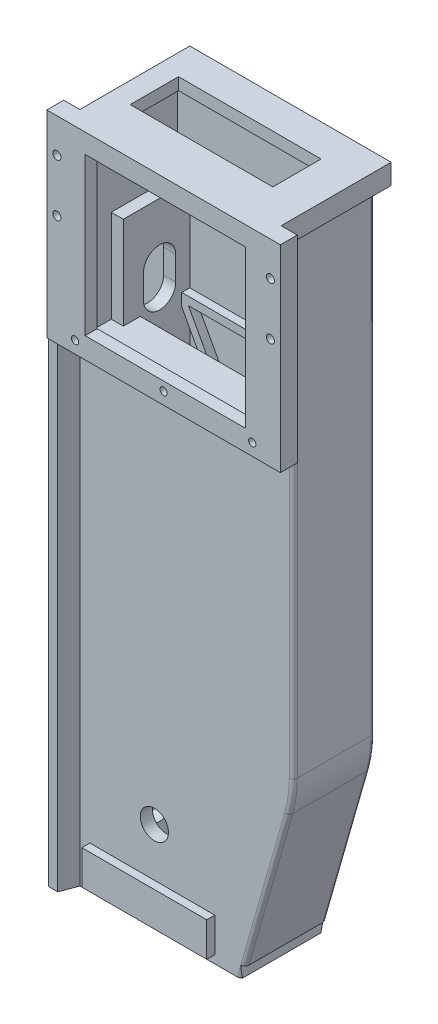
SolidWorks part; units mm, degrees
ref_plane "前视基准面" through (0, 0, 0) normal (0, 0, 1) x (1, 0, 0)
ref_plane "上视基准面" through (0, 0, 0) normal (0, 1, 0) x (1, 0, 0)
ref_plane "右视基准面" through (0, 0, 0) normal (1, 0, 0) x (0, 0, -1)
sketch "草图2" plane through (0, 0, 0) normal (0, 1, 0) x (1, 0, 0)
  line L0 (-163.1117, 0) -> (416.8883, 0)
  line L1 (-55, 0) -> (55, 0) construction
  line L2 (416.8883, 0) -> (416.8883, 42)
  line L3 (416.8883, 42) -> (376.8883, 42)
  line L4 (376.8883, 42) -> (376.8883, 315)
  line L5 (376.8883, 315) -> (-123.1117, 315)
  line L6 (-123.1117, 315) -> (-123.1117, 42)
  line L7 (-123.1117, 42) -> (-163.1117, 42)
  line L8 (-163.1117, 42) -> (-163.1117, 0)
  dimension "D2" = 40
  dimension "D3" = 40
  dimension "D4" = 315
  dimension "D5" = 42
  dimension "D6" = 42
  dimension "D11" = 500
sketch "草图3" plane through (0, 0, 0) normal (0, 1, 0) x (1, 0, 0)
  line L0 (-123.1117, 315) -> (-123.1117, 42) construction
  line L1 (-71.1117, 235) -> (282.8883, 235)
  line L2 (-71.1117, 235) -> (-71.1117, 115)
  line L3 (-71.1117, 115) -> (282.8883, 115)
  line L4 (282.8883, 235) -> (282.8883, 115)
  line L5 (-163.1117, 0) -> (416.8883, 0) construction
  dimension "D1" = 52
  dimension "D2" = 115
  dimension "D3" = 354
  dimension "D4" = 120
extrude "凸台-拉伸1" add sketch "草图2" against normal blind 50
sketch "草图5" plane through (0, -50, 0) normal (0, -1, 0) x (1, 0, 0)
  line L0 (-123.1117, -285) -> (366.8883, -285)
  line L1 (-123.1117, -315) -> (-123.1117, -42) construction
  line L2 (376.8883, -315) -> (-123.1117, -315) construction
  line L3 (376.8883, -42) -> (376.8883, -315) construction
  line L4 (366.8883, -285) -> (366.8883, -42)
  line L5 (366.8883, -42) -> (416.8883, -42)
  line L6 (416.8883, -42) -> (416.8883, 0)
  line L7 (55, 0) -> (-55, 0) construction
  line L8 (416.8883, 0) -> (-163.1117, 0)
  line L9 (-163.1117, -42) -> (-163.1117, 0) construction
  line L10 (-163.1117, 0) -> (-163.1117, -42)
  line L11 (-163.1117, -42) -> (-123.1117, -42)
  line L12 (-123.1117, -42) -> (-123.1117, -285)
  dimension "D1" = 30
  dimension "D2" = 10
extrude "凸台-拉伸2" add sketch "草图5" along normal blind 440
sketch "草图6" plane through (0, -490, 0) normal (0, -1, 0) x (1, 0, 0)
  line L0 (366.8883, -285) -> (366.8883, -82)
  line L1 (366.8883, -285) -> (366.8883, -42) construction
  line L2 (366.8883, -82) -> (-123.1117, -82)
  line L3 (-123.1117, -42) -> (-123.1117, -285) construction
  line L4 (-123.1117, -82) -> (-123.1117, -285)
  line L5 (-123.1117, -285) -> (366.8883, -285)
  line L6 (366.8883, -42) -> (416.8883, -42) construction
  dimension "D1" = 40
extrude "凸台-拉伸3" add sketch "草图6" along normal blind 1220
sketch "草图7" plane through (0, 0, -285) normal (0, 0, -1) x (-1, 0, 0)
  line L0 (-236.8883, -1680) -> (-246.8883, -1680)
  line L1 (123.1117, -1710) -> (-366.8883, -1710) construction
  line L2 (-236.8883, -1710) -> (-236.8883, -1680)
  line L4 (-366.8883, -1710) -> (-366.8883, -50) construction
  line L5 (-366.8883, -1260) -> (-366.8883, -1710)
  line L6 (-366.8883, -1710) -> (-236.8883, -1710)
  line L7 (-246.8883, -1680) -> (-366.8883, -1260)
  dimension "D1" = 360
  dimension "D2" = 30
  dimension "D3" = 450
  dimension "D4" = 10
extrude "切除-拉伸3" cut sketch "草图7" against normal up to next
fillet "圆角1" radius 300 1 edges at (366.8883, -1260, -183.5)
fillet "圆角5" radius 10 3 edges at (366.8883, -633.9918, -285) (363.9886, -1259.5939, -285) (301.1169, -1490.1999, -285)
fillet "圆角6" radius 10 3 edges at (301.1169, -1490.1999, -82) (363.9886, -1259.5939, -82) (366.8883, -853.9918, -82)
sketch "草图8" plane through (-123.1117, 0, 0) normal (-1, 0, 0) x (0, 0, 1)
  line L0 (-82, -1710) -> (-285, -1710) construction
  line L1 (-120, -1710) -> (-240, -1710)
  line L2 (-120, -1710) -> (-120, -260)
  line L3 (-120, -260) -> (-240, -260)
  line L4 (-240, -1710) -> (-240, -260)
  line L5 (55, 0) -> (-55, 0) construction
  line L6 (-285, -1710) -> (-285, -50) construction
  dimension "D1" = 260
  dimension "D2" = 45
  dimension "D3" = 120
extrude "切除-拉伸4" cut sketch "草图8" against normal blind 30
shell "抽壳3" thickness 30 removed face at (25.2308, -1710, -182.1)
ref_plane "基准面1" through (0, -260, 0) normal (0, 1, 0) x (1, 0, 0)
sketch "草图9" plane through (0, -260, 0) normal (0, 1, 0) x (1, 0, 0)
  line L0 (-123.1117, 285) -> (-153.1117, 285)
  line L1 (-153.1117, 285) -> (-168.1117, 319.5)
  line L2 (-168.1117, 319.5) -> (-198.1117, 319.5)
  line L3 (-198.1117, 319.5) -> (-198.1117, 349.5)
  line L4 (-198.1117, 349.5) -> (-228.1117, 349.5)
  line L5 (-228.1117, 349.5) -> (-228.1117, 227.5)
  line L6 (-228.1117, 227.5) -> (-191.1117, 227.5)
  line L7 (-191.1117, 227.5) -> (-191.1117, 240)
  line L8 (-191.1117, 240) -> (-123.1117, 240)
  line L9 (-123.1117, 240) -> (-123.1117, 285)
  dimension "D1" = 30
  dimension "D2" = 30
  dimension "D3" = 30
  dimension "D4" = 105
  dimension "D5" = 30
  dimension "D6" = 37
  dimension "D7" = 12.5
  dimension "D8" = 122
extrude "凸台-拉伸4" add sketch "草图9" against normal up to surface (1450 mm away) up to face at (71.8883, -1710, -183.5)
sketch "草图10" plane through (0, -260, 0) normal (0, -1, 0) x (1, 0, 0)
  line L0 (-116.1117, -240) -> (-116.1117, -285)
  line L1 (-93.1117, -240) -> (-191.1117, -240) construction
  line L2 (-191.1117, -240) -> (-123.1117, -240) construction
  line L3 (-123.1117, -285) -> (-153.1117, -285) construction
  line L4 (-153.1117, -285) -> (227.9167, -285) construction
  line L5 (-116.1117, -285) -> (-153.1117, -285)
  line L6 (-153.1117, -285) -> (-168.1117, -319.5)
  line L7 (-168.1117, -319.5) -> (-198.1117, -319.5)
  line L8 (-198.1117, -319.5) -> (-198.1117, -349.5)
  line L9 (-198.1117, -349.5) -> (-228.1117, -349.5)
  line L10 (-228.1117, -349.5) -> (-228.1117, -227.5)
  line L11 (-228.1117, -227.5) -> (-191.1117, -227.5)
  line L12 (-191.1117, -227.5) -> (-191.1117, -240)
  line L13 (-191.1117, -240) -> (-116.1117, -240)
sketch "草图12" plane through (0, -1710, 0) normal (0, -1, 0) x (1, 0, 0)
  line L0 (-123.1117, -82) -> (-163.1117, -82)
  line L7 (-228.1117, -74.5) -> (-228.1117, -139.5)
  line L8 (-228.1117, -139.5) -> (-191.1117, -139.5)
  line L9 (-191.1117, -139.5) -> (-191.1117, -127)
  line L10 (-191.1117, -127) -> (-176.1117, -127)
  line L11 (-176.1117, -127) -> (-176.1117, -120)
  line L12 (-176.1117, -120) -> (-123.1117, -120)
  line L13 (-123.1117, -120) -> (-123.1117, -82)
  line L14 (-163.1117, -82) -> (-178.1117, -42)
  line L15 (-178.1117, -42) -> (-203.1117, -42)
  line L16 (-203.1117, -42) -> (-203.1117, -82)
  line L17 (-228.1117, -74.5) -> (-201.014, -88.7528)
  line L18 (-201.014, -88.7528) -> (-198.6865, -84.3276)
  line L19 (-198.6865, -84.3276) -> (-203.1117, -82)
  point P3 (-190.6117, -42)
  dimension "D1" = 40
  dimension "D2" = 15
  dimension "D3" = 105
  dimension "D4" = 37
  dimension "D5" = 12.5
  dimension "D6" = 65
  dimension "D7" = 7
  dimension "D8" = 15
  dimension "D9" = 40
  dimension "D10" = 25
  dimension "D11" = 40
  dimension "D12" = 5
  dimension "D13" = 5
extrude "凸台-拉伸7" add sketch "草图12" against normal up to surface (1450 mm away) up to plane "基准面1"
sketch "草图13" plane through (0, 0, -285) normal (0, 0, -1) x (-1, 0, 0)
  line L0 (-376.8883, -50) -> (123.1117, -50) construction
  line L4 (123.1117, -260) -> (123.1117, -50) construction
  line L5 (153.1117, -1710) -> (-227.9167, -1710) construction
  line L6 (153.1117, -1710) -> (153.1117, -260) construction
  circle A0 centre (-21.8883, -1485) radius 35
  circle A1 centre (-21.8883, -265) radius 35
  dimension "D1" = 70
  dimension "D2" = 70
  dimension "D5" = 225
  dimension "D6" = 175
  dimension "D3" = 215
  dimension "D4" = 145
extrude "切除-拉伸5" cut sketch "草图13" against normal through all
extrude "切除-拉伸1" cut sketch "草图3" against normal blind 50
sketch "草图15" plane through (0, 0, 0) normal (0, 0, 1) x (1, 0, 0)
  line L0 (-163.1117, 0) -> (416.8883, 0) construction
  line L1 (329.8883, -438) -> (-68.1117, -438)
  line L2 (329.8883, -438) -> (329.8883, -48)
  line L3 (329.8883, -48) -> (-68.1117, -48)
  line L4 (-68.1117, -438) -> (-68.1117, -48)
  line L5 (-163.1117, -490) -> (-163.1117, 0) construction
  dimension "D1" = 398
  dimension "D2" = 390
  dimension "D3" = 48
  dimension "D4" = 95
extrude "切除-拉伸6" cut sketch "草图15" against normal up to surface (30 mm away)
sketch "草图17" plane through (-93.1117, 0, 0) normal (-1, 0, 0) x (0, 0, 1)
  line L0 (-140, -370) -> (-140, -430)
  line L1 (-220, -430) -> (-220, -370)
  line L2 (-140, -600) -> (-140, -720)
  line L3 (-220, -720) -> (-220, -600)
  line L4 (-180, -525.5736) -> (-180, -50525.5736) construction
  line L5 (-140, -1120) -> (-140, -1000)
  line L6 (-220, -1000) -> (-220, -1120)
  line L7 (-140, -1530) -> (-140, -1430)
  line L8 (-220, -1530) -> (-220, -1430)
  line L9 (173.25, -260) -> (-173.25, -260) construction
  arc A0 (-140, -370) -> (-220, -370) centre (-180, -370) ccw
  arc A1 (-220, -430) -> (-140, -430) centre (-180, -430) ccw
  arc A2 (-140, -600) -> (-220, -600) centre (-180, -600) ccw
  arc A3 (-220, -720) -> (-140, -720) centre (-180, -720) ccw
  arc A4 (-140, -1000) -> (-220, -1000) centre (-180, -1000) ccw
  arc A5 (-220, -1120) -> (-140, -1120) centre (-180, -1120) ccw
  arc A6 (-140, -1430) -> (-220, -1430) centre (-180, -1430) ccw
  arc A7 (-220, -1530) -> (-140, -1530) centre (-180, -1530) ccw
  point P1 (-180, -330)
  point P9 (-180, -560)
  point P11 (-180, -470)
  point P13 (-180, -760)
  point P15 (-180, -960)
  point P17 (-180, -1160)
  point P34 (-180, -1390)
  dimension "D1" = 80
  dimension "D2" = 70
  dimension "D3" = 60
  dimension "D4" = 90
  dimension "D5" = 120
  dimension "D6" = 120
  dimension "D7" = 200
  dimension "D8" = 100
  dimension "D9" = 230
extrude "切除-拉伸7" cut sketch "草图17" against normal up to next
sketch "草图18" plane through (0, -1710, 0) normal (0, -1, 0) x (1, 0, 0)
  line L0 (236.8883, -86.9418) -> (236.8883, -280.0582) construction
  line L1 (206.8883, -255) -> (-63.1117, -255)
  line L2 (206.8883, -255) -> (206.8883, -112)
  line L3 (206.8883, -112) -> (-63.1117, -112)
  line L4 (-63.1117, -255) -> (-63.1117, -112)
  line L5 (181.8883, -245) -> (1.8883, -245)
  line L6 (181.8883, -245) -> (181.8883, -122)
  line L7 (181.8883, -122) -> (1.8883, -122)
  line L8 (1.8883, -245) -> (1.8883, -122)
  line L9 (-153.1117, -285) -> (227.9167, -285) construction
  line L11 (227.9167, -82) -> (-163.1117, -82) construction
  line L12 (-93.1117, -120) -> (-93.1117, -240) construction
  point P18 (-93.1117, -180)
  point P23 (-291.4725, -200.257)
  point P24 (-46.1117, -222)
  dimension "D1" = 55
  dimension "D2" = 40
  dimension "D3" = 40
  dimension "D4" = 95
extrude "凸台-拉伸8" add sketch "草图18" against normal blind 30
hole_wizard "M16 螺纹孔1" positions "草图21" profile "草图22" tap size "M16" standard "ISO" end condition through all
sketch "草图21" plane through (0, -1710, 0) normal (0, -1, 0) x (-1, 0, 0)
  point P0 (46.1447, 221.9951)
sketch "草图22" plane through (-46.1447, -1710, -221.9951) normal (1, 0, 0) x (0, 0, -1)
  line L0 (0, 0) -> (0, 1710)
  line L1 (0, 1710) -> (7, 1710)
  line L2 (7, 1710) -> (7, 0)
  line L5 (7, 0) -> (0, 0)
  line L11 (0, -6.35) -> (0, 107.95) construction
  dimension "螺纹线主直径" = 14
  dimension "通孔螺纹孔钻头深度" = 1710
chamfer "倒角1" distance 2 angle 45 5 edges at (-228.1117, -985, -227.5) (-228.1117, -985, -139.5) (-203.1117, -985, -42) (-228.1117, -985, -74.5) (-228.1117, -985, -349.5) first distance on face at (-209.6117, -985, -227.5) first distance on face at (-209.6117, -985, -139.5) first distance on face at (-203.1117, -985, -62) first distance on face at (-228.1117, -985, -107) first distance on face at (-213.1117, -985, -349.5)
ref_plane "基准面2" through (0, 0, -235) normal (0, 0, 1) x (1, 0, 0)
sketch "草图25" plane through (0, 0, -235) normal (0, 0, 1) x (1, 0, 0)
  line L0 (336.8883, -470) -> (-63.1117, -470)
  line L1 (336.8883, -30) -> (336.8883, -1217.9835) construction
  line L2 (-63.1117, -230) -> (-63.1117, -1680) construction
  line L3 (336.8883, -1210) -> (-56.1117, -1210)
  line L4 (282.8883, 0) -> (-71.1117, 0) construction
  line L5 (1.8883, -1710) -> (181.8883, -1710) construction
  dimension "D1" = 470
  dimension "D2" = 500
rib "筋10" sketch "草图25" sketch "草图25" thickness 20 extrusion direction normal to sketch draft on no parameters "D1"=20
sketch "草图26" plane through (0, 0, -235) normal (0, 0, 1) x (1, 0, 0)
  line L0 (336.8883, -1208.9918) -> (-63.1117, -470)
  line L1 (336.8883, -1217.9835) -> (336.8883, -1200) construction
  line L2 (-63.1117, -480) -> (-63.1117, -460) construction
  line L3 (336.8883, -470) -> (-63.1117, -1210)
  line L4 (336.8883, -480) -> (336.8883, -460) construction
  line L5 (-63.1117, -1220) -> (-63.1117, -1200) construction
rib "筋11" sketch "草图26" sketch "草图26" thickness 20 extrusion direction normal to sketch draft on no parameters "D1"=20
ref_plane "基准面3" through (0, 0, -132) normal (0, 0, -1) x (-1, 0, 0)
sketch "草图27" plane through (0, 0, -132) normal (0, 0, -1) x (-1, 0, 0)
  line L0 (63.1117, -470) -> (-336.8883, -470)
  line L1 (-336.8883, -1217.9835) -> (-336.8883, -460) construction
  line L3 (-336.8883, -1210) -> (63.1117, -1210)
  line L4 (63.1117, -460) -> (63.1117, -1680) construction
  line L7 (71.1117, 0) -> (-282.8883, 0) construction
  line L8 (-181.8883, -1710) -> (-1.8883, -1710) construction
  dimension "D1" = 470
  dimension "D2" = 500
rib "筋12" sketch "草图27" sketch "草图27" thickness 20 extrusion direction normal to sketch draft on no parameters "D1"=20
sketch "草图29" plane through (0, 0, -132) normal (0, 0, -1) x (-1, 0, 0)
  line L0 (63.1117, -1210) -> (-336.8883, -470)
  line L1 (63.1117, -1200) -> (63.1117, -1220) construction
  line L2 (-336.8883, -460) -> (-336.8883, -480) construction
  line L3 (63.1117, -470) -> (-336.8883, -1208.9918)
  line L4 (63.1117, -460) -> (63.1117, -480) construction
  line L5 (-336.8883, -1200) -> (-336.8883, -1217.9835) construction
rib "筋13" sketch "草图29" sketch "草图29" thickness 20 extrusion direction normal to sketch draft on no parameters "D1"=20
sketch "草图30" plane through (0, 0, -82) normal (0, 0, 1) x (1, 0, 0)
  line L0 (-163.1117, -260) -> (-163.1117, -1710) construction
  line L1 (171.8883, -1690) -> (-138.1117, -1690)
  line L2 (171.8883, -1690) -> (171.8883, -1605)
  line L3 (171.8883, -1605) -> (-138.1117, -1605)
  line L4 (-138.1117, -1690) -> (-138.1117, -1605)
  line L5 (227.9167, -1710) -> (-163.1117, -1710) construction
  dimension "D1" = 310
  dimension "D2" = 85
  dimension "D3" = 25
  dimension "D4" = 20
extrude "凸台-拉伸9" add sketch "草图30" along normal blind 20
sketch "草图31" plane through (0, 0, 0) normal (0, 0, 1) x (1, 0, 0)
  line L0 (416.8883, -490) -> (-163.1117, -490) construction
  line L1 (356.8883, -490) -> (-123.1117, -490) construction
  line L2 (-163.1117, -490) -> (-163.1117, 0) construction
  line L3 (-163.1117, 0) -> (416.8883, 0) construction
  line L4 (416.8883, -490) -> (416.8883, 0) construction
  circle A0 centre (346.8883, -460) radius 9
  circle A1 centre (126.8883, -460) radius 9
  circle A2 centre (-93.1117, -460) radius 9
  circle A3 centre (-138.1117, -215) radius 10
  circle A4 centre (-138.1117, -85) radius 10
  circle A5 centre (391.8883, -215) radius 10
  circle A6 centre (391.8883, -85) radius 10
  dimension "D1" = 18
  dimension "D2" = 18
  dimension "D3" = 18
  dimension "D4" = 30
  dimension "D10" = 20
  dimension "D11" = 20
  dimension "D12" = 20
  dimension "D13" = 20
  dimension "D20" = 25
  dimension "D21" = 25
  dimension "D5" = 30
  dimension "D6" = 30
  dimension "D7" = 70
  dimension "D8" = 220
  dimension "D9" = 220
  dimension "D14" = 25
  dimension "D15" = 25
  dimension "D16" = 85
  dimension "D17" = 215
  dimension "D18" = 85
  dimension "D19" = 215
extrude "切除-拉伸8" cut sketch "草图31" against normal up to surface (42 mm away) up to face at (-143.1117, -245, -42)
sketch "草图32" plane through (0, -1710, 0) normal (0, -1, 0) x (1, 0, 0)
  line L1 (236.8883, -86.9418) -> (236.8883, -280.0582) construction
  line L2 (227.9167, -82) -> (-163.1117, -82) construction
  line L3 (-228.1117, -76.5) -> (-228.1117, -137.5) construction
  line L4 (-178.1117, -42) -> (-201.1117, -42) construction
  circle A0 centre (-188.1117, -112) radius 7
  circle A1 centre (141.8883, -107) radius 7
  dimension "D1" = 95
  dimension "D3" = 14
  dimension "D4" = 14
  dimension "D2" = 25
  dimension "D5" = 40
  dimension "D6" = 70
extrude "切除-拉伸9" cut sketch "草图32" against normal blind 30
